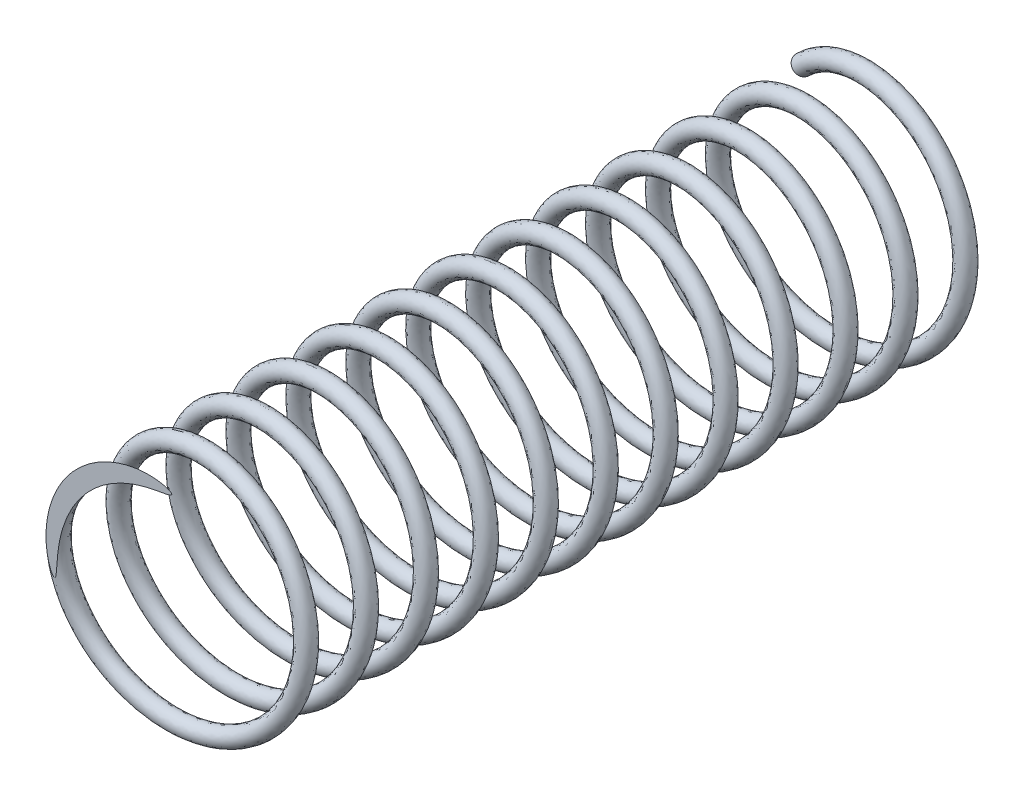
SolidWorks part; units mm, degrees
note: '?' marks a value the reader was unsure of.
ref_plane "前视基准面" through (0, 0, 0) normal (0, 0, 1) x (1, 0, 0)
ref_plane "上视基准面" through (0, 0, 0) normal (0, 1, 0) x (1, 0, 0)
ref_plane "右视基准面" through (0, 0, 0) normal (1, 0, 0) x (0, 0, -1)
sketch "草图1" plane through (0, 0, 0) normal (0, 0, 1) x (1, 0, 0)
  circle A0 centre (0, 0) radius 9
  dimension "D1" = 18
curve "螺旋线/涡状线1" pitch 5 height 76.25 turns 15.25
ref_plane "基准面1" through (-6.364, 6.364, 0) normal (0.7044, 0.7044, 0.0881) x (0.7098, -0.6989, -0.0874)
sketch "草图2" plane through (-6.364, 6.364, 0) normal (0.7044, 0.7044, 0.0881) x (0.7098, -0.6989, -0.0874)
  circle A0 centre (-0.0316, -0.0404) radius 0.75
  spline S1 degree 3 poles (-0.0316, -0.0404) (-0.0316, -0.0405) (-0.0287, -0.0401) (-0.0259, -0.0398) (-0.0245, -0.0396) (-0.0202, -0.0392) (-0.0174, -0.0389) (-0.0088, -0.038) (-0.0031, -0.0375) (0.0139, -0.0357) (0.0253, -0.0346) (0.0594, -0.0312) (0.0822, -0.029) (0.1505, -0.0224) (0.1961, -0.0181) (0.3327, -0.0053) (0.4238, 0.0029) (0.6972, 0.0272) (0.8796, 0.0426) (1.4267, 0.0873) (1.7916, 0.115) (2.8867, 0.1932) (3.6173, 0.2386) (5.8099, 0.3572) (7.2729, 0.4133) (10.2002, 0.4671) (11.6648, 0.4672) (13.8589, 0.3799) (14.5899, 0.3368) (15.6821, 0.2244) (16.0454, 0.1789) (16.5867, 0.0872) (16.7665, 0.0527) (17.1231, -0.0296) (17.3002, -0.0768) (17.559, -0.1681) (17.6442, -0.202) (17.8089, -0.2816) (17.8891, -0.3271) (18.0317, -0.4418) (18.0962, -0.5136) (18.1332, -0.6458) (18.1341, -0.6928) (18.1155, -0.7824) (18.0967, -0.8248) (18.026, -0.9425) (17.9612, -1.0089) (17.8232, -1.1291) (17.7488, -1.1828) (17.519, -1.3328) (17.3568, -1.4185) (16.8622, -1.6566) (16.5207, -1.7898) (15.8315, -2.0363) (15.483, -2.1484) (14.4319, -2.4655) (13.7237, -2.6517) (12.3016, -2.9987) (11.5872, -3.1586) (9.4387, -3.6119) (7.999, -3.8788) (5.1121, -4.3662) (3.6647, -4.5868) (1.851, -4.8291) (1.488, -4.8758) (0.9431, -4.9421) (0.7614, -4.9636) (0.5568, -4.9863) (0.5341, -4.9888) (0.5056, -4.9919) (0.4999, -4.9925) (0.4886, -4.9937) (0.4884, -4.9937) (0.5054, -4.992) (0.5168, -4.9908) (0.5737, -4.9851) (0.6192, -4.9807) (0.7559, -4.9677) (0.847, -4.9593) (1.6671, -4.8854) (2.397, -4.8304) (4.5878, -4.6825) (6.05, -4.6082) (8.9761, -4.5099) (10.4402, -4.4852) (12.6359, -4.51) (13.3677, -4.5287) (14.8298, -4.6009) (15.5606, -4.6521) (16.65, -4.7886) (17.0122, -4.8437) (17.5486, -4.9603) (17.7263, -5.0049) (18.0746, -5.1174) (18.2475, -5.1832) (18.4777, -5.3328) (18.5507, -5.3921) (18.6237, -5.5083) (18.6409, -5.5519) (18.6519, -5.6428) (18.6454, -5.6892) (18.601, -5.8191) (18.5425, -5.893) (18.4141, -6.0233) (18.3422, -6.0805) (18.1182, -6.2392) (17.9575, -6.328) (17.6303, -6.4918) (17.4629, -6.5662) (16.9558, -6.7764) (16.6109, -6.8995) (15.9159, -7.1292) (15.5655, -7.2352) (14.5099, -7.537) (13.8002, -7.7168) (11.663, -8.2209) (10.2275, -8.5102) (7.3478, -9.0385) (5.9032, -9.2763) (3.7311, -9.5983) (3.0062, -9.6997) (1.9173, -9.8404) (1.5541, -9.8856) (1.145, -9.9321) (1.0996, -9.9371) (1.0427, -9.9434) (1.0313, -9.9446) (1.0086, -9.947) (1.0085, -9.947) (1.0427, -9.9436) (1.0654, -9.9413) (1.1792, -9.9301) (1.2703, -9.9216) (1.5437, -9.8965) (1.726, -9.8807) (3.3671, -9.743) (4.8284, -9.6522) (7.7529, -9.514) (9.2163, -9.468) (11.412, -9.4476) (12.144, -9.449) (13.6077, -9.4749) (14.3394, -9.4993) (15.8006, -9.5873) (16.531, -9.6477) (17.6161, -9.8152) (17.977, -9.8823) (18.503, -10.0392) (18.6769, -10.1003) (18.9174, -10.2324) (18.9948, -10.2835) (19.0898, -10.3825) (19.1177, -10.4196) (19.1567, -10.5024) (19.167, -10.5482) (19.1622, -10.6854) (19.1153, -10.7701) (19.0011, -10.913) (18.9324, -10.9745) (18.7161, -11.1435) (18.5571, -11.2359) (18.0706, -11.4902) (17.7307, -11.6282) (16.7016, -12.0107) (15.999, -12.2191) (14.5867, -12.6043) (13.8756, -12.7783) (12.4485, -13.1043) (11.7324, -13.2562) (9.5795, -13.6881) (8.1379, -13.9445) (5.2477, -14.4116) (3.799, -14.624) (2.1647, -14.8268) (1.983, -14.8488) (1.7104, -14.8803) (1.6196, -14.8907) (1.5229, -14.901) (1.5226, -14.901) (1.534, -14.8998) (1.5397, -14.8993) (1.5568, -14.8975) (1.5681, -14.8964) (1.6023, -14.893) (1.625, -14.8908) (1.6933, -14.8842) (1.7389, -14.8799) (2.1488, -14.8415) (2.5135, -14.811) (3.608, -14.7245) (4.3383, -14.6745) (6.5301, -14.5421) (7.9928, -14.4772) (10.9195, -14.4012) (12.3839, -14.3889) (14.579, -14.4434) (15.3106, -14.4738) (16.4056, -14.5536) (16.7702, -14.5859) (17.4973, -14.6698) (17.86, -14.7206) (18.3988, -14.8257) (18.5776, -14.8656) (18.9303, -14.9632) (19.1051, -15.0201) (19.3528, -15.1384) (19.4332, -15.1834) (19.577, -15.2965) (19.6427, -15.367) (19.6835, -15.498) (19.6861, -15.5449) (19.6699, -15.635) (19.652, -15.6778) (19.5833, -15.7966) (19.519, -15.8637) (19.3131, -16.0452) (19.1559, -16.1417) (18.8351, -16.3177) (18.6695, -16.3961) (18.1667, -16.6164) (17.8231, -16.7435) (16.784, -17.0978) (16.0792, -17.2974) (14.6629, -17.6676) (13.9505, -17.8362) (11.8068, -18.3117) (10.369, -18.5891) (7.4854, -19.0955) (6.0393, -19.3241) (3.8649, -19.6305) (3.1393, -19.7271) (2.3215, -19.8232) (2.2306, -19.8336) (2.117, -19.8463) (2.0942, -19.8488) (2.0488, -19.8537) (2.0483, -19.8538) (2.1165, -19.8469) (2.1621, -19.8425) (2.3898, -19.8207) (2.572, -19.8044) (3.1189, -19.7572) (3.4838, -19.7283) (5.3085, -19.592) (6.7703, -19.5095) (9.6957, -19.3919) (11.1595, -19.3566) (13.3553, -19.3583) (14.0873, -19.368) (15.5504, -19.4158) (16.2817, -19.4529) (17.3754, -19.5489) (17.7394, -19.5879) (18.4641, -19.6903) (18.8256, -19.752) (19.357, -19.8894) (19.5328, -19.9425) (19.7855, -20.0496) (19.868, -20.0899) (20.0222, -20.1884) (20.0957, -20.2468) (20.1713, -20.3614) (20.1898, -20.4044) (20.2037, -20.4948) (20.1986, -20.5415) (20.1573, -20.6724) (20.0997, -20.7471) (19.9723, -20.8785) (19.9006, -20.9361) (19.7517, -21.0424) (19.6741, -21.0911) (19.4366, -21.2287) (19.2721, -21.3095) (18.9387, -21.4602) (18.7694, -21.5298) (18.2575, -21.7282) (17.911, -21.8464) (16.8645, -22.1785) (16.1578, -22.3705) (14.0282, -22.9059) (12.595, -23.2072) (9.7193, -23.7571) (8.2761, -24.0036) (6.1061, -24.3391) (5.3819, -24.4452) (4.2941, -24.5942) (3.9313, -24.6422) (3.3867, -24.711) (3.2051, -24.7334) (2.9325, -24.7659) (2.8416, -24.7765) (2.7053, -24.792) (2.6598, -24.7971) (2.603, -24.8033) (2.5916, -24.8046) (2.5746, -24.8064) (2.5689, -24.807) (2.5575, -24.8082) (2.5568, -24.8083) (2.5853, -24.8054) (2.608, -24.8031) (3.3592, -24.7291) (4.0891, -24.6733) (5.5493, -24.5701) (6.2799, -24.5251) (8.4726, -24.4077) (9.9357, -24.3525) (12.863, -24.3008) (14.3276, -24.3018) (16.5215, -24.3925) (17.2525, -24.4369) (18.3443, -24.553) (18.7075, -24.6) (19.2481, -24.6953) (19.4276, -24.7312) (19.7833, -24.8175) (19.9598, -24.8672) (20.2163, -24.9649) (20.3004, -25.0014) (20.4613, -25.0886) (20.5391, -25.139) (20.6356, -25.2365) (20.6642, -25.273) (20.7054, -25.3547) (20.7172, -25.4001) (20.7168, -25.5374) (20.6716, -25.6233) (20.5591, -25.7676) (20.4907, -25.8296) (20.3471, -25.9429) (20.2711, -25.9942) (20.0375, -26.1382) (19.8742, -26.2216) (19.3768, -26.454) (19.0347, -26.5853) (18.3444, -26.8287) (17.9956, -26.9397) (16.9436, -27.254) (16.2352, -27.4391) (14.8125, -27.7841) (14.098, -27.9433) (11.9491, -28.3947) (10.5093, -28.6607) (7.6221, -29.1464) (6.1746, -29.3662) (4.3607, -29.6072) (3.9976, -29.6537) (3.4526, -29.7194) (3.2709, -29.7408) (3.0776, -29.7616) (3.0768, -29.7617) (3.0995, -29.7594) (3.1109, -29.7582) (3.145, -29.7548) (3.1678, -29.7526) (3.2361, -29.7459) (3.2816, -29.7416) (3.4183, -29.7288) (3.5094, -29.7205) (4.3296, -29.6476) (5.0595, -29.593) (7.2505, -29.4464) (8.7127, -29.373) (11.6389, -29.2765) (13.103, -29.2528) (15.2986, -29.2799) (16.0304, -29.2995) (17.4924, -29.3742) (18.2231, -29.4269) (19.3119, -29.5681) (19.6739, -29.625) (20.2091, -29.7471) (20.3863, -29.7938) (20.6457, -29.8837) (20.731, -29.9171) (20.8965, -29.9952) (20.9771, -30.0397) (21.1221, -30.1513) (21.1888, -30.2203) (21.2336, -30.3501) (21.2378, -30.3969) (21.2242, -30.4874) (21.2072, -30.5307) (21.1405, -30.6506) (21.0767, -30.7183) (20.9402, -30.8402) (20.8663, -30.8945) (20.6374, -31.046) (20.4755, -31.1323) (20.1462, -31.2919) (19.9782, -31.3648) (19.4696, -31.5713) (19.1242, -31.693) (18.4284, -31.9201) (18.0777, -32.0252) (17.0215, -32.3247) (16.3115, -32.5035) (14.1737, -33.0049) (12.738, -33.2933) (9.8579, -33.8196) (8.4132, -34.0566) (6.2409, -34.3773) (5.5159, -34.4783) (4.4269, -34.6181) (4.0637, -34.6632) (3.6773, -34.7062) (3.6545, -34.7088) (3.6204, -34.7125) (3.6091, -34.7137) (3.5949, -34.7152) (3.592, -34.7155) (3.5877, -34.716) (3.591, -34.7156) (3.5938, -34.7153) (3.5953, -34.7152) (3.6024, -34.7145) (3.6081, -34.7139) (3.6593, -34.7087) (3.7048, -34.7043) (3.8414, -34.6912) (3.9325, -34.6827) (4.2059, -34.658) (4.3882, -34.6423) (6.0294, -34.5061) (7.4908, -34.416) (10.4153, -34.2795) (11.8788, -34.2344) (14.0745, -34.2158) (14.8066, -34.2178) (16.2702, -34.2454) (17.0019, -34.2707) (18.0976, -34.3389) (18.4626, -34.3667) (19.1911, -34.4382) (19.5546, -34.4816) (20.0967, -34.5685) (20.2768, -34.6011) (20.6346, -34.6781) (20.8124, -34.7222) (21.1612, -34.8331) (21.3343, -34.898) (21.5667, -35.044) (21.6407, -35.1016) (21.7188, -35.2144) (21.7385, -35.2568) (21.7551, -35.3468) (21.7516, -35.3936) (21.7136, -35.5255) (21.6567, -35.6012) (21.5305, -35.7336) (21.4591, -35.7915) (21.2364, -35.952) (21.076, -36.0415) (20.5859, -36.2887) (20.2454, -36.4247) (19.2143, -36.8019) (18.5113, -37.0087) (17.0983, -37.3912) (16.3869, -37.5643) (14.9595, -37.8888) (14.2433, -38.0401) (12.09, -38.4702) (10.6483, -38.7257) (7.7578, -39.1912) (6.309, -39.4031) (4.6745, -39.6043) (4.4928, -39.6261) (4.2656, -39.652) (4.2201, -39.6571) (4.1519, -39.6646) (4.1292, -39.667) (4.105, -39.6696) (4.1081, -39.6693) (4.1109, -39.669) (4.1124, -39.6688) (4.1166, -39.6684) (4.1195, -39.6681) (4.128, -39.6672) (4.1337, -39.6667) (4.1508, -39.665) (4.1622, -39.6638) (4.2646, -39.6537) (4.3557, -39.6451) (4.8112, -39.6032) (5.1759, -39.5729) (6.2705, -39.4873) (7.0008, -39.4377) (9.1927, -39.3066) (10.6554, -39.2425) (13.5822, -39.1685) (15.0466, -39.1573) (17.2416, -39.2145) (17.9731, -39.246) (19.068, -39.3283) (19.4325, -39.3617) (20.1593, -39.4483) (20.5218, -39.5009) (21.0597, -39.6104) (21.2381, -39.6521) (21.5892, -39.7553) (21.7632, -39.8156) (22.0053, -39.9449) (22.0834, -39.9946) (22.1814, -40.0907) (22.2107, -40.1266) (22.2539, -40.2072) (22.2672, -40.2523) (22.2711, -40.3895) (22.2276, -40.4766) (22.1169, -40.6222) (22.0489, -40.6847) (21.8343, -40.8558) (21.6756, -40.9489) (21.3519, -41.1196) (21.1856, -41.1963) (20.6809, -41.4123) (20.3368, -41.5377) (19.2962, -41.8879) (18.5911, -42.0862) (17.1742, -42.454) (16.4616, -42.6218) (14.3174, -43.0951) (12.8794, -43.3714) (9.9955, -43.876) (8.5492, -44.1039) (6.3747, -44.4089) (5.6491, -44.5053) (4.8311, -44.6002) (4.7402, -44.6105) (4.6436, -44.621) (4.6379, -44.6216) (4.6294, -44.6225) (4.6265, -44.6228) (4.6223, -44.6232) (4.6252, -44.6229) (4.628, -44.6226) (4.6295, -44.6225) (4.6423, -44.6212) (4.6536, -44.62) (4.6878, -44.6166) (4.7105, -44.6144) (4.7788, -44.6077) (4.8244, -44.6034) (5.0521, -44.582) (5.2344, -44.5659) (5.7814, -44.5192) (6.1462, -44.4905) (7.9711, -44.3555) (9.4329, -44.2738) (12.3583, -44.1579) (13.8221, -44.1236) (16.018, -44.1273) (16.7499, -44.1378) (18.213, -44.1876) (18.9442, -44.2259) (20.0376, -44.325) (20.4015, -44.3652) (21.1258, -44.4712) (21.487, -44.5351) (22.0165, -44.6798) (22.1915, -44.736) (22.4402, -44.852) (22.5211, -44.896) (22.6672, -45.0061) (22.7349, -45.0739) (22.7834, -45.2023) (22.7892, -45.2489) (22.7782, -45.3398) (22.7623, -45.3835) (22.6977, -45.5046) (22.6344, -45.5729) (22.4309, -45.7571) (22.2741, -45.8544) (21.7939, -46.1204) (21.455, -46.2615) (20.771, -46.5219) (20.424, -46.6388) (19.3765, -46.9677) (18.6694, -47.1584) (16.5391, -47.6907) (15.1057, -47.9908) (12.2296, -48.5386) (10.7863, -48.7844) (8.616, -49.1186) (7.8917, -49.2243) (6.8039, -49.3726) (6.441, -49.4204) (5.8964, -49.4887) (5.7147, -49.5109) (5.4421, -49.543) (5.3512, -49.5535) (5.2376, -49.5662) (5.2149, -49.5687) (5.1807, -49.5724) (5.1694, -49.5737) (5.1524, -49.5755) (5.1466, -49.5761) (5.1395, -49.5769) (5.1423, -49.5766) (5.1451, -49.5763) (5.1466, -49.5761) (5.1508, -49.5757) (5.1537, -49.5754) (5.202, -49.5705) (5.2476, -49.5661) (6.0217, -49.4916) (6.7515, -49.4357) (8.2118, -49.3334) (8.9425, -49.2888) (11.1352, -49.1727) (12.5983, -49.1183) (15.5257, -49.0688) (16.9903, -49.071) (19.1841, -49.1651) (19.915, -49.2109) (21.0064, -49.3308) (21.3694, -49.3793) (21.9093, -49.4784) (22.0886, -49.5158) (22.4431, -49.6064) (22.619, -49.6588) (22.8725, -49.764) (22.9554, -49.8035) (23.1111, -49.8997) (23.1856, -49.9564) (23.266, -50.0676) (23.2868, -50.1094) (23.3063, -50.1988) (23.3044, -50.2457) (23.2697, -50.3785) (23.2137, -50.4551) (23.0887, -50.5887) (23.0176, -50.647) (22.8695, -50.7546) (22.7922, -50.8037) (22.5554, -50.9424) (22.3911, -51.0237) (21.8914, -51.2509) (21.5486, -51.3804) (20.8573, -51.6208) (20.5081, -51.7307) (19.4553, -52.0423) (18.7466, -52.2263) (17.3236, -52.5694) (16.6089, -52.7279) (14.4596, -53.1774) (13.0196, -53.4425) (10.1321, -53.9265) (8.6845, -54.1455) (6.8704, -54.3853) (6.5073, -54.4315) (6.0531, -54.4857) (5.9622, -54.4963) (5.8259, -54.5119) (5.7804, -54.517) (5.7122, -54.5245) (5.6895, -54.527) (5.6639, -54.5298) (5.661, -54.5301) (5.6568, -54.5305) (5.6594, -54.5302) (5.6623, -54.5299) (5.6637, -54.5298) (5.6708, -54.5291) (5.6765, -54.5285) (5.6935, -54.5268) (5.7049, -54.5256) (5.8984, -54.5064) (6.0806, -54.4899) (6.9921, -54.4099) (7.722, -54.3557) (9.913, -54.2105) (11.3753, -54.1378) (14.3016, -54.0431) (15.7657, -54.0205) (17.9613, -54.0499) (18.6931, -54.0705) (20.1549, -54.1477) (20.8856, -54.2019) (21.9737, -54.348) (22.3355, -54.4068) (22.8693, -54.5347) (23.046, -54.5839) (23.3031, -54.6801) (23.3874, -54.7159) (23.5493, -54.8012) (23.6277, -54.8504) (23.727, -54.9451) (23.7569, -54.9804) (23.8022, -55.0599) (23.8169, -55.1045) (23.8252, -55.2415) (23.7835, -55.3298) (23.6746, -55.4768) (23.607, -55.5397) (23.4645, -55.6545) (23.3889, -55.7063) (23.156, -55.8517) (22.993, -55.9355) (22.6618, -56.0913) (22.4933, -56.1628) (21.9833, -56.3659) (21.6374, -56.4861) (20.9408, -56.7109) (20.5899, -56.8151) (19.533, -57.1123) (18.8228, -57.2901) (16.6844, -57.7889) (15.2485, -58.0762) (12.3681, -58.6007) (10.9232, -58.8369) (8.7507, -59.1563) (8.0257, -59.2569) (6.9366, -59.3958) (6.5734, -59.4409) (6.1982, -59.4816) (6.1868, -59.4828) (6.174, -59.4841) (6.1765, -59.4839) (6.1793, -59.4836) (6.1808, -59.4834) (6.185, -59.483) (6.1879, -59.4827) (6.1964, -59.4819) (6.2021, -59.4813) (6.2305, -59.4784) (6.2533, -59.4762) (6.3216, -59.4695) (6.3671, -59.4651) (6.5038, -59.4523) (6.5949, -59.444) (6.8683, -59.4196) (7.0506, -59.4041) (8.692, -59.2693) (10.1533, -59.1798) (13.078, -59.045) (14.5415, -59.0008) (16.7372, -58.984) (17.4692, -58.9866) (18.9328, -59.0159) (19.6645, -59.0423) (20.7601, -59.1127) (21.1251, -59.1414) (21.8533, -59.2152) (22.2167, -59.26) (22.7582, -59.3502) (22.9381, -59.3841) (23.2951, -59.4646) (23.4724, -59.5108) (23.7322, -59.5994) (23.8178, -59.6322) (23.9839, -59.7088) (24.065, -59.7524) (24.2122, -59.8611) (24.2808, -59.9276) (24.3329, -60.0545) (24.3403, -60.101) (24.332, -60.1921) (24.3171, -60.2362) (24.2548, -60.3585) (24.192, -60.4275) (24.0572, -60.5511) (23.9836, -60.606) (23.7558, -60.7592) (23.5942, -60.846) (23.1009, -61.0868) (22.7597, -61.2208) (21.7267, -61.5929) (21.0234, -61.7983) (19.6097, -62.1782) (18.8981, -62.3503) (17.4703, -62.6732) (16.7539, -62.8239) (14.6003, -63.2523) (13.1585, -63.507) (10.2677, -63.9708) (8.8189, -64.1821) (7.1842, -64.3817) (7.0024, -64.4033) (6.7979, -64.4262) (6.7751, -64.4287) (6.741, -64.4324) (6.7299, -64.4336) (6.7128, -64.4355) (6.7069, -64.4361) (6.6984, -64.437) (6.6955, -64.4373) (6.6912, -64.4378) (6.6933, -64.4376) (6.6962, -64.4373) (6.6976, -64.4371) (6.7445, -64.4323) (6.7901, -64.4279) (6.9267, -64.4147) (7.0178, -64.4062) (7.4734, -64.3649) (7.8381, -64.3349) (8.9328, -64.2501) (9.6631, -64.201) (11.855, -64.0711) (13.3178, -64.0078) (16.2447, -63.9358) (17.709, -63.9256) (19.904, -63.9857) (20.6355, -64.0183) (21.7301, -64.1032) (22.0946, -64.1376) (22.821, -64.2272) (23.1833, -64.2815) (23.7202, -64.3958) (23.8982, -64.4394) (24.2474, -64.5488) (24.4207, -64.6128) (24.6553, -64.7553) (24.7302, -64.8112) (24.8129, -64.9207) (24.8349, -64.9619) (24.8572, -65.0506) (24.8569, -65.0976) (24.8258, -65.2313) (24.7708, -65.3088) (24.647, -65.4436) (24.5762, -65.5023) (24.3548, -65.6646) (24.1948, -65.7547) (23.8686, -65.9206) (23.7016, -65.9957) (23.1952, -66.2077) (22.8505, -66.3315) (21.8086, -66.6778) (21.1031, -66.8747) (19.6856, -67.2403) (18.9729, -67.4072) (16.8282, -67.8784) (15.3901, -68.1537) (12.5058, -68.6566) (11.0594, -68.8837) (8.8847, -69.1873) (8.1591, -69.2834) (7.3864, -69.3718) (7.3409, -69.3769) (7.2727, -69.3845) (7.25, -69.387) (7.2216, -69.39) (7.2159, -69.3906) (7.2074, -69.3915) (7.2133, -69.3909) (7.219, -69.3903) (7.2218, -69.3901) (7.2361, -69.3886) (7.2474, -69.3875) (7.3499, -69.3773) (7.4409, -69.3686) (7.7142, -69.3434) (7.8965, -69.3275) (8.4436, -69.2813) (8.8084, -69.2529) (10.6334, -69.1191) (12.0952, -69.0381) (15.0208, -68.924) (16.4846, -68.8907) (18.6804, -68.8964) (19.4124, -68.9076) (20.8753, -68.9595) (21.6065, -68.999) (22.6997, -69.1013) (23.0634, -69.1428) (23.7871, -69.2526) (24.1481, -69.3187) (24.6753, -69.4715) (24.8495, -69.5309) (25.0931, -69.6575) (25.1717, -69.7061) (25.2724, -69.7993) (25.3029, -69.834) (25.3501, -69.9124) (25.3662, -69.9565) (25.3747, -70.0476) (25.3671, -70.0938) (25.3358, -70.1798) (25.3127, -70.2198) (25.2325, -70.3311) (25.1653, -70.3946) (24.9525, -70.5679) (24.7942, -70.6618) (24.3096, -70.9197) (23.97, -71.0586) (23.2845, -71.3153) (22.9371, -71.4309) (21.8886, -71.7566) (21.1813, -71.9462) (19.0502, -72.4754) (17.6165, -72.7744) (14.7401, -73.3201) (13.2966, -73.565) (11.1262, -73.8981) (10.4018, -74.0033) (9.3139, -74.1509) (8.951, -74.1984) (8.4063, -74.2662) (8.2246, -74.2883) (7.952, -74.32) (7.8611, -74.3304) (7.7587, -74.3415) (7.7474, -74.3428) (7.7331, -74.3443) (7.7303, -74.3446) (7.7246, -74.3452) (7.7304, -74.3446) (7.7389, -74.3437) (7.7446, -74.3431) (7.7731, -74.3402) (7.7958, -74.338) (7.8641, -74.3313) (7.9096, -74.3269) (8.6839, -74.2539) (9.4138, -74.1981) (10.8741, -74.0967) (11.6048, -74.0526) (13.7976, -73.9377) (15.2607, -73.8842) (16.7244, -73.8605) knots 0 0 0 0 0.000004 0.000004 0.000009 0.000009 0.000017 0.000017 0.000034 0.000034 0.000069 0.000069 0.000137 0.000137 0.000274 0.000274 0.000549 0.000549 0.001098 0.001098 0.002196 0.002196 0.004392 0.004392 0.008783 0.008783 0.013175 0.013175 0.015371 0.015371 0.016469 0.016469 0.017018 0.017018 0.017567 0.017567 0.017841 0.017841 0.018116 0.018116 0.01839 0.01839 0.018527 0.018527 0.018664 0.018664 0.018939 0.018939 0.019213 0.019213 0.019762 0.019762 0.02086 0.02086 0.021958 0.021958 0.024154 0.024154 0.02635 0.02635 0.030741 0.030741 0.035133 0.035133 0.036231 0.036231 0.03678 0.03678 0.036849 0.036849 0.036866 0.036866 0.036883 0.036883 0.036917 0.036917 0.037054 0.037054 0.037329 0.037329 0.039525 0.039525 0.043916 0.043916 0.048308 0.048308 0.050504 0.050504 0.0527 0.0527 0.053798 0.053798 0.054347 0.054347 0.054895 0.054895 0.05517 0.05517 0.055307 0.055307 0.055444 0.055444 0.055719 0.055719 0.055993 0.055993 0.056542 0.056542 0.057091 0.057091 0.058189 0.058189 0.059287 0.059287 0.061483 0.061483 0.065875 0.065875 0.070266 0.070266 0.072462 0.072462 0.07356 0.07356 0.073697 0.073697 0.073731 0.073731 0.073766 0.073766 0.073834 0.073834 0.074109 0.074109 0.074658 0.074658 0.079049 0.079049 0.083441 0.083441 0.085637 0.085637 0.087833 0.087833 0.090029 0.090029 0.091126 0.091126 0.091675 0.091675 0.09195 0.09195 0.092087 0.092087 0.092224 0.092224 0.092499 0.092499 0.092773 0.092773 0.093322 0.093322 0.09442 0.09442 0.096616 0.096616 0.098812 0.098812 0.101008 0.101008 0.105399 0.105399 0.109791 0.109791 0.11034 0.11034 0.110614 0.110614 0.110632 0.110632 0.110649 0.110649 0.110683 0.110683 0.110752 0.110752 0.110889 0.110889 0.111987 0.111987 0.114183 0.114183 0.118574 0.118574 0.122966 0.122966 0.125162 0.125162 0.12626 0.12626 0.127357 0.127357 0.127906 0.127906 0.128455 0.128455 0.12873 0.12873 0.129004 0.129004 0.129142 0.129142 0.129279 0.129279 0.129553 0.129553 0.130102 0.130102 0.130651 0.130651 0.131749 0.131749 0.133945 0.133945 0.136141 0.136141 0.140532 0.140532 0.144924 0.144924 0.14712 0.14712 0.147394 0.147394 0.147463 0.147463 0.147532 0.147532 0.147669 0.147669 0.148218 0.148218 0.149316 0.149316 0.153707 0.153707 0.158099 0.158099 0.160295 0.160295 0.162491 0.162491 0.163588 0.163588 0.164686 0.164686 0.165235 0.165235 0.16551 0.16551 0.165784 0.165784 0.165922 0.165922 0.166059 0.166059 0.166333 0.166333 0.166608 0.166608 0.166882 0.166882 0.167431 0.167431 0.16798 0.16798 0.169078 0.169078 0.171274 0.171274 0.175665 0.175665 0.180057 0.180057 0.182253 0.182253 0.183351 0.183351 0.1839 0.1839 0.184174 0.184174 0.184312 0.184312 0.184346 0.184346 0.184363 0.184363 0.18438 0.18438 0.184449 0.184449 0.186645 0.186645 0.18884 0.18884 0.193232 0.193232 0.197624 0.197624 0.199819 0.199819 0.200917 0.200917 0.201466 0.201466 0.202015 0.202015 0.20229 0.20229 0.202564 0.202564 0.202701 0.202701 0.202839 0.202839 0.203113 0.203113 0.203388 0.203388 0.203662 0.203662 0.204211 0.204211 0.205309 0.205309 0.206407 0.206407 0.208603 0.208603 0.210799 0.210799 0.21519 0.21519 0.219582 0.219582 0.22068 0.22068 0.221229 0.221229 0.221263 0.221263 0.221297 0.221297 0.221366 0.221366 0.221503 0.221503 0.221778 0.221778 0.223973 0.223973 0.228365 0.228365 0.232757 0.232757 0.234953 0.234953 0.237148 0.237148 0.238246 0.238246 0.238795 0.238795 0.23907 0.23907 0.239344 0.239344 0.239619 0.239619 0.239756 0.239756 0.239893 0.239893 0.240168 0.240168 0.240442 0.240442 0.240991 0.240991 0.24154 0.24154 0.242638 0.242638 0.243736 0.243736 0.245932 0.245932 0.250323 0.250323 0.254715 0.254715 0.256911 0.256911 0.258009 0.258009 0.258077 0.258077 0.258112 0.258112 0.25812 0.25812 0.258124 0.258124 0.258129 0.258129 0.258146 0.258146 0.258283 0.258283 0.258558 0.258558 0.259107 0.259107 0.263498 0.263498 0.26789 0.26789 0.270086 0.270086 0.272281 0.272281 0.273379 0.273379 0.274477 0.274477 0.275026 0.275026 0.275575 0.275575 0.276124 0.276124 0.276399 0.276399 0.276536 0.276536 0.276673 0.276673 0.276948 0.276948 0.277222 0.277222 0.277771 0.277771 0.278869 0.278869 0.281065 0.281065 0.283261 0.283261 0.285456 0.285456 0.289848 0.289848 0.29424 0.29424 0.294789 0.294789 0.294926 0.294926 0.294994 0.294994 0.294999 0.294999 0.295003 0.295003 0.295012 0.295012 0.295029 0.295029 0.295063 0.295063 0.295338 0.295338 0.296435 0.296435 0.298631 0.298631 0.303023 0.303023 0.307415 0.307415 0.30961 0.30961 0.310708 0.310708 0.311806 0.311806 0.312355 0.312355 0.312904 0.312904 0.313179 0.313179 0.313316 0.313316 0.313453 0.313453 0.313728 0.313728 0.314002 0.314002 0.314551 0.314551 0.3151 0.3151 0.316198 0.316198 0.318394 0.318394 0.320589 0.320589 0.324981 0.324981 0.329373 0.329373 0.331569 0.331569 0.331843 0.331843 0.33186 0.33186 0.331869 0.331869 0.331873 0.331873 0.331877 0.331877 0.331912 0.331912 0.33198 0.33198 0.332118 0.332118 0.332666 0.332666 0.333764 0.333764 0.338156 0.338156 0.342548 0.342548 0.344743 0.344743 0.346939 0.346939 0.348037 0.348037 0.349135 0.349135 0.349684 0.349684 0.349959 0.349959 0.350233 0.350233 0.35037 0.35037 0.350508 0.350508 0.350782 0.350782 0.351331 0.351331 0.352429 0.352429 0.353527 0.353527 0.355723 0.355723 0.360114 0.360114 0.364506 0.364506 0.366702 0.366702 0.3678 0.3678 0.368349 0.368349 0.368623 0.368623 0.368692 0.368692 0.368726 0.368726 0.368743 0.368743 0.368747 0.368747 0.368752 0.368752 0.36876 0.36876 0.368898 0.368898 0.371093 0.371093 0.373289 0.373289 0.377681 0.377681 0.382072 0.382072 0.384268 0.384268 0.385366 0.385366 0.385915 0.385915 0.386464 0.386464 0.386739 0.386739 0.387013 0.387013 0.38715 0.38715 0.387287 0.387287 0.387562 0.387562 0.387836 0.387836 0.388111 0.388111 0.38866 0.38866 0.389758 0.389758 0.390856 0.390856 0.393052 0.393052 0.395247 0.395247 0.399639 0.399639 0.404031 0.404031 0.405129 0.405129 0.405403 0.405403 0.40554 0.40554 0.405609 0.405609 0.405617 0.405617 0.405622 0.405622 0.405626 0.405626 0.405643 0.405643 0.405677 0.405677 0.406226 0.406226 0.408422 0.408422 0.412814 0.412814 0.417206 0.417206 0.419401 0.419401 0.421597 0.421597 0.422695 0.422695 0.423244 0.423244 0.423518 0.423518 0.423793 0.423793 0.42393 0.42393 0.424067 0.424067 0.424342 0.424342 0.424616 0.424616 0.424891 0.424891 0.42544 0.42544 0.425989 0.425989 0.427087 0.427087 0.428185 0.428185 0.43038 0.43038 0.434772 0.434772 0.439164 0.439164 0.44136 0.44136 0.442457 0.442457 0.442492 0.442492 0.442496 0.442496 0.4425 0.4425 0.442509 0.442509 0.442526 0.442526 0.442595 0.442595 0.442732 0.442732 0.443006 0.443006 0.443555 0.443555 0.447947 0.447947 0.452339 0.452339 0.454534 0.454534 0.45673 0.45673 0.457828 0.457828 0.458926 0.458926 0.459475 0.459475 0.460024 0.460024 0.460298 0.460298 0.460573 0.460573 0.460847 0.460847 0.460985 0.460985 0.461122 0.461122 0.461396 0.461396 0.461671 0.461671 0.46222 0.46222 0.463318 0.463318 0.465514 0.465514 0.467709 0.467709 0.469905 0.469905 0.474297 0.474297 0.478688 0.478688 0.479237 0.479237 0.479306 0.479306 0.47934 0.47934 0.479357 0.479357 0.479366 0.479366 0.47937 0.47937 0.479375 0.479375 0.479512 0.479512 0.479786 0.479786 0.480884 0.480884 0.48308 0.48308 0.487472 0.487472 0.491863 0.491863 0.494059 0.494059 0.495157 0.495157 0.496255 0.496255 0.496804 0.496804 0.497353 0.497353 0.497627 0.497627 0.497765 0.497765 0.497902 0.497902 0.498176 0.498176 0.498451 0.498451 0.499 0.499 0.499549 0.499549 0.500647 0.500647 0.502842 0.502842 0.505038 0.505038 0.50943 0.50943 0.513822 0.513822 0.516017 0.516017 0.516155 0.516155 0.516223 0.516223 0.51624 0.51624 0.516249 0.516249 0.516258 0.516258 0.516292 0.516292 0.516566 0.516566 0.517115 0.517115 0.518213 0.518213 0.522605 0.522605 0.526996 0.526996 0.529192 0.529192 0.531388 0.531388 0.532486 0.532486 0.533584 0.533584 0.534133 0.534133 0.534407 0.534407 0.534545 0.534545 0.534682 0.534682 0.534819 0.534819 0.534956 0.534956 0.535231 0.535231 0.53578 0.53578 0.536878 0.536878 0.537976 0.537976 0.540171 0.540171 0.544563 0.544563 0.548955 0.548955 0.55115 0.55115 0.552248 0.552248 0.552797 0.552797 0.553072 0.553072 0.553106 0.553106 0.553115 0.553115 0.553123 0.553123 0.55314 0.55314 0.553209 0.553209 0.553346 0.553346 0.555542 0.555542 0.557738 0.557738 0.56213 0.56213 0.56213 0.56213 construction
  dimension "D1" = 1.5
sweep "扫描1" add profiles "草图2" path "螺旋线/涡状线1"
ref_plane "基准面2" through (0, 0, 0) normal (0, 0, 1) x (1, 0, 0)
ref_axis "基准轴1" through (0, 0, 0) along (0, 0, 1)?
sketch "草图3" plane through (0, 0, 0) normal (1, 0, 0) x (0, 0, -1)
  line L0 (-60, -31.0515) -> (-60, 27.3888)
  dimension "D1" = 60
extrude "切除-拉伸1" cut sketch "草图3" against normal through all and the other way through all
